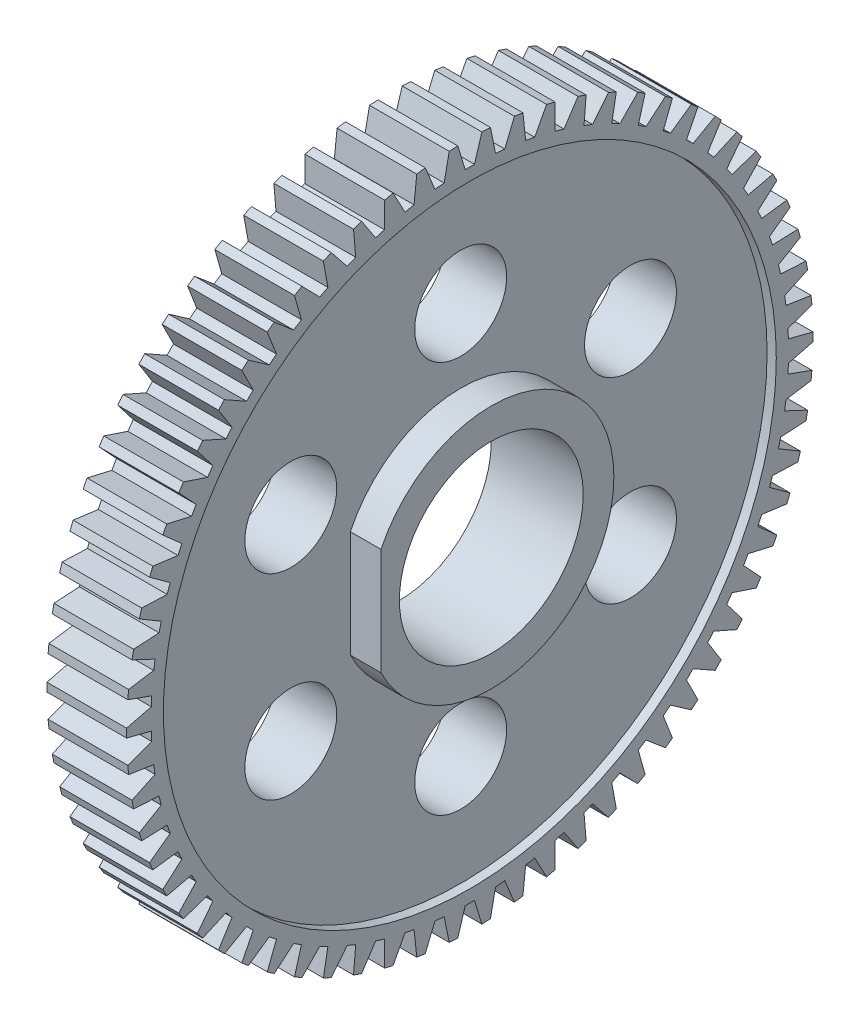
SolidWorks part; units mm, degrees
material "AISI 4140 Steel, quenched & tempered"
ref_plane "Front Plane" through (0, 0, 0) normal (1, 0, 0) x (0, 1, 0)
ref_plane "Top Plane" through (0, 0, 0) normal (0, 0, 1) x (0, 1, 0)
ref_plane "Right Plane" through (0, 0, 0) normal (0, 1, 0) x (-1, 0, 0)
sketch "Sketch1" plane through (0, 0, 0) normal (1, 0, 0) x (0, 1, 0)
  line L0 (0, 15.697) -> (0, -56.4932) construction
  line L1 (-65.019, 0) -> (64.3815, 0) construction
  line L2 (-8.7178, 18) -> (8.7178, 18)
  circle A0 centre (0, 0) radius 50
  circle A1 centre (0, 0) radius 15
  arc A2 (-8.7178, 18) -> (8.7178, 18) centre (0, 0) ccw
  circle A3 centre (32, 0) radius 7.5
  circle A4 centre (0, 0) radius 20 construction
  circle A5 centre (16, -27.7128) radius 7.5
  circle A6 centre (-16, -27.7128) radius 7.5
  circle A7 centre (-32, 0) radius 7.5
  circle A8 centre (-16, 27.7128) radius 7.5
  circle A9 centre (16, 27.7128) radius 7.5
  point P11 (20, 0)
  point P27 (0, 0)
  dimension "D1" = 100
  dimension "D2" = 30
  dimension "D6" = 15
  dimension "D4" = 18
  dimension "D5" = 32
  dimension "D3" = 5
  dimension "D7" = 6
extrude "Boss-Extrude1" add sketch "Sketch1" along normal blind 10 contours A0 A9 A8 A7 A6 A5 A3 A2 L2 region at (0, -48.5858, 0)
extrude "Boss-Extrude2" add sketch "Sketch1<3>" along normal blind 15 contours L2 A2 A1 region at (0, 0, 17.4483)
sketch "Sketch1<3>" plane through (0, 0, 0) normal (1, 0, 0) x (0, 1, 0) same geometry as "Sketch1"
sketch "Sketch4" plane through (0, 0, 0) normal (0, 1, 0) x (-1, 0, 0)
  line L0 (1.5, 52) -> (-11.5, 52)
  line L1 (-11.5, 52) -> (-11.5, 50)
  line L2 (-11.5, 50) -> (1.5, 50)
  line L3 (1.5, 50) -> (1.5, 52)
  line L5 (-22.1123, 0) -> (24.3581, 0) construction
  dimension "D1" = 52
  dimension "D2" = 50
  dimension "D3" = 13
  dimension "D4" = 1.5
revolve "Revolve1" add sketch "Sketch4" angle 360 about L5
sketch "Sketch2" plane through (10, 0, 0) normal (1, 0, 0) x (0, 1, 0)
  line L0 (0, 63.7991) -> (0, 0) construction
  line L1 (0, 0) -> (59.3534, 0) construction
  line L2 (-0.7, 55.9956) -> (-1.7214, 51.9715)
  line L3 (-0.7, 55.9956) -> (0.7, 55.9956)
  line L5 (0.7, 55.9956) -> (1.7214, 51.9715)
  circle A0 centre (0, 0) radius 52
  arc A1 (56, 0) -> (0.7, 55.9956) centre (0, 0) ccw
  circle A3 centre (0, 0) radius 56 construction
  point P9 (53.5531, 16.3728)
  dimension "D1" = 104
  dimension "D3" = 0.7
  dimension "D2" = 4
extrude "Boss-Extrude3" add sketch "Sketch2" against normal up to surface (11.5 mm away) from surface contours L5 A1 L2 A0 region at (10, 0, 53.7123) up to face at (-1.5, 0, -52) starting at face at (11.5, 0, -50)
pattern_circular "CirPattern1" count 66 over 360 about axis through (11.5, 0, 0) along (1, 0, 0) of "Boss-Extrude3"
ref_axis "Axis1" through (-2.4, 0, 0) along (1, 0, 0)
